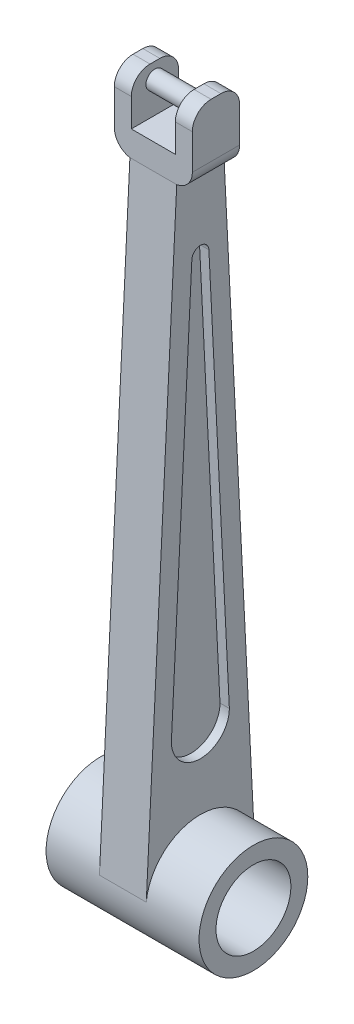
SolidWorks part; units mm, degrees
ref_plane "Ön Düzlem" through (0, 0, 0) normal (0, 0, 1) x (1, 0, 0)
ref_plane "Üst Düzlem" through (0, 0, 0) normal (0, 1, 0) x (1, 0, 0)
ref_plane "Sağ Düzlem" through (0, 0, 0) normal (1, 0, 0) x (0, 0, -1)
sketch "Çizim1" plane through (0, 0, 0) normal (1, 0, 0) x (0, 0, -1)
  line L0 (0, 59.789) -> (0, -59.789) construction
  line L1 (-3.6821, 104.0511) -> (3.6821, 104.0511)
  line L5 (-1.3645, 90.3955) -> (-4.6437, 25.1419)
  line L6 (-3.6821, 104.0511) -> (-8.7073, 4.0511)
  line L7 (3.6821, 104.0511) -> (8.7073, 4.0511)
  line L10 (1.3645, 90.3955) -> (4.6437, 25.1419)
  line L12 (0, 104.0511) -> (0, 20.4982) construction
  line L13 (-0.8291, 101.0511) -> (-5.5528, 7.0511) construction
  line L14 (0.8291, 101.0511) -> (5.5528, 7.0511) construction
  line L15 (-0.8291, 101.0511) -> (0.8291, 101.0511) construction
  line L16 (-5.5528, 7.0511) -> (5.5528, 7.0511) construction
  line L17 (-8.7073, 4.0511) -> (8.7073, 4.0511) construction
  line L19 (-3.7848, 106.0944) -> (3.7848, 106.0944)
  line L20 (-3.7848, 106.0944) -> (-3.7848, 102.0078)
  line L21 (-3.7848, 102.0078) -> (3.7848, 102.0078)
  line L22 (3.7848, 106.0944) -> (3.7848, 102.0078)
  line L23 (-3.7848, 106.0944) -> (3.7848, 102.0078) construction
  line L24 (-3.7848, 102.0078) -> (3.7848, 106.0944) construction
  arc A0 (-1.3645, 90.3955) -> (1.3645, 90.3955) centre (0, 90.3269) cw
  arc A3 (-8.7073, 4.0511) -> (8.7073, 4.0511) centre (0, 4.0511) ccw
  arc A4 (-4.6437, 25.1419) -> (4.6437, 25.1419) centre (0, 25.1419) ccw
  point P0 (0, 54.0511)
  dimension "D2" = 3
extrude "Yükseklik-Ekstrüzyon2" add sketch "Çizim1" along normal mid plane 7.5 contours L6 L7 L1 L5 A0 L10 region at (0, 100.927, 0)
extrude "Yükseklik-Ekstrüzyon3" add sketch "Çizim1<5>" along normal mid plane 4.5 contours L10 A4 L5 A0
sketch "Çizim1<5>" plane through (0, 0, 0) normal (1, 0, 0) x (0, 0, -1) same geometry as "Çizim1"
sketch "Çizim4" plane through (3.75, 0, 0) normal (1, 0, 0) x (0, 0, -1)
  circle A0 centre (0, 4.0511) radius 6
extrude "Kes-Ekstrüzyon1" cut sketch "Çizim4" against normal blind 15.5
sketch "Çizim5" plane through (3.75, 0, 0) normal (1, 0, 0) x (0, 0, -1)
  circle A0 centre (0, 4.0511) radius 8.7073
  circle A1 centre (0, 4.0511) radius 6 construction
  circle A2 centre (0, 4.0511) radius 6
extrude "Yükseklik-Ekstrüzyon5" add sketch "Çizim5" along normal blind 8.5 and the other way blind 16
extrude "Yükseklik-Ekstrüzyon6" add sketch "Çizim1<6>" along normal mid plane 12.5 contours L19 L22 L21 L20
sketch "Çizim1<6>" plane through (0, 0, 0) normal (1, 0, 0) x (0, 0, -1) same geometry as "Çizim1"
sketch "Çizim6" plane through (0, 106.0944, 0) normal (0, 1, 0) x (1, 0, 0)
  line L0 (6.25, 3.7848) -> (-6.25, 3.7848) construction
  line L1 (-6.25, 3.7848) -> (-3.525, 3.7848)
  line L2 (-6.25, 3.7848) -> (-6.25, -3.7848)
  line L3 (-6.25, -3.7848) -> (-3.525, -3.7848)
  line L4 (-3.525, 3.7848) -> (-3.525, -3.7848)
  line L5 (-6.25, -3.7848) -> (-6.25, 3.7848) construction
  line L6 (3.75, -3.7848) -> (-3.75, -3.7848) construction
  line L8 (0, -9.5781) -> (0, 9.5781) construction
  line L9 (6.25, 3.7848) -> (6.25, -3.7848)
  line L10 (6.25, 3.7848) -> (3.525, 3.7848)
  line L11 (6.25, -3.7848) -> (3.525, -3.7848)
  line L12 (3.525, 3.7848) -> (3.525, -3.7848)
extrude "Yükseklik-Ekstrüzyon7" add sketch "Çizim6" along normal blind 7.5
sketch "Çizim7" plane through (-3.525, 0, 0) normal (1, 0, 0) x (0, 0, -1)
  line L0 (0, 113.5944) -> (0, 106.0944) construction
  line L1 (-3.7848, 113.5944) -> (3.7848, 113.5944) construction
  line L2 (-3.7848, 106.0944) -> (3.7848, 106.0944) construction
  circle A0 centre (0, 111.0769) radius 1.4412
extrude "Yükseklik-Ekstrüzyon8" add sketch "Çizim7" along normal blind 8.5
fillet "Radyus1" radius 3 6 edges at (6.25, 102.0078, 0) (-6.25, 102.0078, 0) (4.8875, 113.5944, 3.7848) (4.8875, 113.5944, -3.7848) (-4.8875, 113.5944, -3.7848) (-4.8875, 113.5944, 3.7848)
